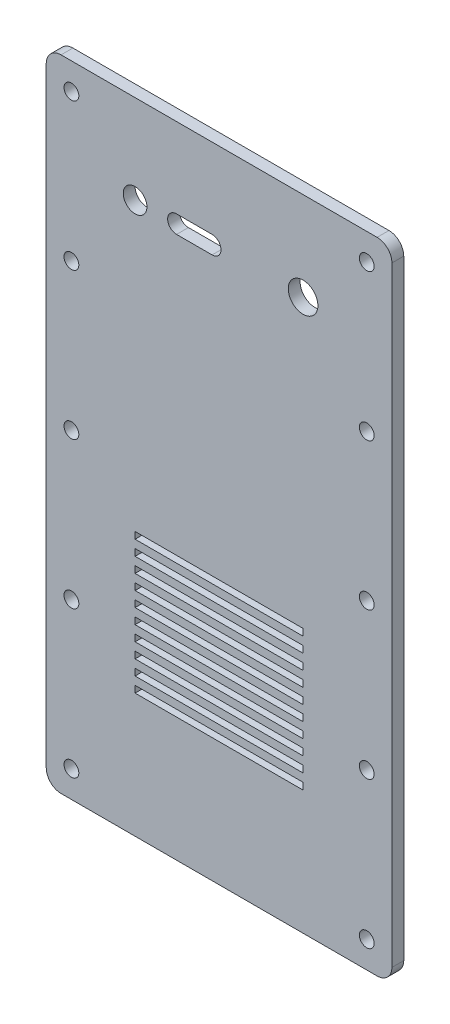
SolidWorks part; units mm, degrees
ref_plane "Front Plane" through (0, 0, 0) normal (0, 0, 1) x (1, 0, 0)
ref_plane "Top Plane" through (0, 0, 0) normal (0, 1, 0) x (1, 0, 0)
ref_plane "Right Plane" through (0, 0, 0) normal (1, 0, 0) x (0, 0, -1)
sketch "Sketch1" plane through (0, 0, 0) normal (0, 0, 1) x (1, 0, 0)
  line L1 (-20.18, -45) -> (20.18, -45) construction
  line L2 (-20.18, -45) -> (-20.18, 45) construction
  line L3 (-20.18, 45) -> (20.18, 45) construction
  line L4 (20.18, -45) -> (20.18, 45) construction
  line L5 (-20.18, -45) -> (20.18, 45) construction
  line L6 (-20.18, 45) -> (20.18, -45) construction
  line L7 (-29.18, 54) -> (29.18, 54)
  line L8 (-29.18, 54) -> (-29.18, -54)
  line L9 (-29.18, -54) -> (29.18, -54)
  line L10 (29.18, 54) -> (29.18, -54)
  line L11 (-29.18, 54) -> (29.18, -54) construction
  line L12 (-29.18, -54) -> (29.18, 54) construction
  point P0 (0, 0)
  point P6 (0, 0)
  dimension "D1" = 90
  dimension "D2" = 40.36
  dimension "D3" = 9
  dimension "D4" = 9
extrude "Boss-Extrude1" add sketch "Sketch1" along normal blind 2
fillet "Fillet1" radius 2.5 4 edges at (-29.18, -54, 1) (29.18, -54, 1) (-29.18, 54, 1) (29.18, 54, 1)
sketch "Sketch2" plane through (0, 0, 2) normal (0, 0, 1) x (1, 0, 0)
  line L0 (-20.18, -45) -> (-20.18, 45) construction
  line L1 (-24.93, -49.5) -> (24.93, -49.5) construction
  line L2 (-24.93, -49.5) -> (-24.93, 49.5) construction
  line L3 (-24.93, 49.5) -> (24.93, 49.5) construction
  line L4 (24.93, -49.5) -> (24.93, 49.5) construction
  line L5 (-24.93, -49.5) -> (24.93, 49.5) construction
  line L6 (-24.93, 49.5) -> (24.93, -49.5) construction
  circle A0 centre (-24.93, 49.5) radius 1.25
  circle A1 centre (24.93, 49.5) radius 1.25
  circle A2 centre (24.93, 24.75) radius 1.25
  circle A3 centre (24.93, 0) radius 1.25
  circle A4 centre (24.93, -24.75) radius 1.25
  circle A5 centre (24.93, -49.5) radius 1.25
  circle A6 centre (-24.93, 24.75) radius 1.25
  circle A7 centre (-24.93, 0) radius 1.25
  circle A8 centre (-24.93, -24.75) radius 1.25
  circle A9 centre (-24.93, -49.5) radius 1.25
  point P0 (0, 0)
  dimension "D3" = 2.5
  dimension "D1" = 4.75
  dimension "D2" = 99
  dimension "D4" = 5
extrude "Cut-Extrude1" cut sketch "Sketch2" against normal up to surface (2 mm away) up to face at (0, 0, 0)
sketch "Sketch3" plane through (0, 0, 2) normal (0, 0, 1) x (1, 0, 0)
  line L0 (-7.18, 39) -> (-1.18, 39) construction
  line L1 (-7.18, 40.5) -> (-1.18, 40.5)
  line L2 (-7.18, 37.5) -> (-1.18, 37.5)
  line L3 (26.68, 54) -> (-26.68, 54) construction
  line L4 (-29.18, 51.5) -> (-29.18, -51.5) construction
  line L5 (29.18, -51.5) -> (29.18, 51.5) construction
  line L6 (-14.18, -13.0694) -> (-14.18, -11.9306)
  line L7 (-14.18, -10.5694) -> (14.18, -10.5694)
  line L8 (-14.18, -10.5694) -> (-14.18, -9.4306)
  line L9 (-14.18, -9.4306) -> (14.18, -9.4306)
  line L10 (14.18, -10.5694) -> (14.18, -9.4306)
  line L11 (-14.18, -10.5694) -> (14.18, -9.4306) construction
  line L12 (-14.18, -9.4306) -> (14.18, -10.5694) construction
  line L13 (-14.18, -13.0694) -> (14.18, -13.0694)
  line L14 (14.18, -13.0694) -> (14.18, -11.9306)
  line L15 (-14.18, -11.9306) -> (14.18, -11.9306)
  line L16 (-14.18, -15.5694) -> (-14.18, -14.4306)
  line L17 (-14.18, -15.5694) -> (14.18, -15.5694)
  line L18 (14.18, -15.5694) -> (14.18, -14.4306)
  line L19 (-14.18, -14.4306) -> (14.18, -14.4306)
  line L20 (-14.18, -18.0694) -> (-14.18, -16.9306)
  line L21 (-14.18, -18.0694) -> (14.18, -18.0694)
  line L22 (14.18, -18.0694) -> (14.18, -16.9306)
  line L23 (-14.18, -16.9306) -> (14.18, -16.9306)
  line L24 (-14.18, -20.5694) -> (-14.18, -19.4306)
  line L25 (-14.18, -20.5694) -> (14.18, -20.5694)
  line L26 (14.18, -20.5694) -> (14.18, -19.4306)
  line L27 (-14.18, -19.4306) -> (14.18, -19.4306)
  line L28 (-14.18, -23.0694) -> (-14.18, -21.9306)
  line L29 (-14.18, -23.0694) -> (14.18, -23.0694)
  line L30 (14.18, -23.0694) -> (14.18, -21.9306)
  line L31 (-14.18, -21.9306) -> (14.18, -21.9306)
  line L32 (-14.18, -25.5694) -> (-14.18, -24.4306)
  line L33 (-14.18, -25.5694) -> (14.18, -25.5694)
  line L34 (14.18, -25.5694) -> (14.18, -24.4306)
  line L35 (-14.18, -24.4306) -> (14.18, -24.4306)
  line L36 (-14.18, -28.0694) -> (-14.18, -26.9306)
  line L37 (-14.18, -28.0694) -> (14.18, -28.0694)
  line L38 (14.18, -28.0694) -> (14.18, -26.9306)
  line L39 (-14.18, -26.9306) -> (14.18, -26.9306)
  line L40 (-14.18, -30.5694) -> (-14.18, -29.4306)
  line L41 (-14.18, -30.5694) -> (14.18, -30.5694)
  line L42 (14.18, -30.5694) -> (14.18, -29.4306)
  line L43 (-14.18, -29.4306) -> (14.18, -29.4306)
  line L44 (-14.18, -33.0694) -> (-14.18, -31.9306)
  line L45 (-14.18, -33.0694) -> (14.18, -33.0694)
  line L46 (14.18, -33.0694) -> (14.18, -31.9306)
  line L47 (-14.18, -31.9306) -> (14.18, -31.9306)
  circle A0 centre (14.18, 39) radius 2.5
  circle A1 centre (-14.18, 39) radius 2
  arc A2 (-7.18, 40.5) -> (-7.18, 37.5) centre (-7.18, 39) ccw
  arc A3 (-1.18, 37.5) -> (-1.18, 40.5) centre (-1.18, 39) ccw
  point P6 (-4.18, 39)
  point P11 (-4.18, 37.5)
  point P21 (0, -10)
  dimension "D1" = 5
  dimension "D2" = 4
  dimension "D3" = 6
  dimension "D4" = 3
  dimension "D5" = 15
  dimension "D6" = 15
  dimension "D7" = 10
  dimension "D8" = 15
  dimension "D9" = 1.1389
  dimension "D10" = 15
  dimension "D11" = 10
  dimension "D13" = 2.5
  dimension "D12" = 10
extrude "Cut-Extrude2" cut sketch "Sketch3" against normal up to surface (2 mm away) up to face at (26.18, -49.5, 0)
equation "\"case_width\"=40.36"
equation "\"D2@Sketch1\"=\"case_width\""
